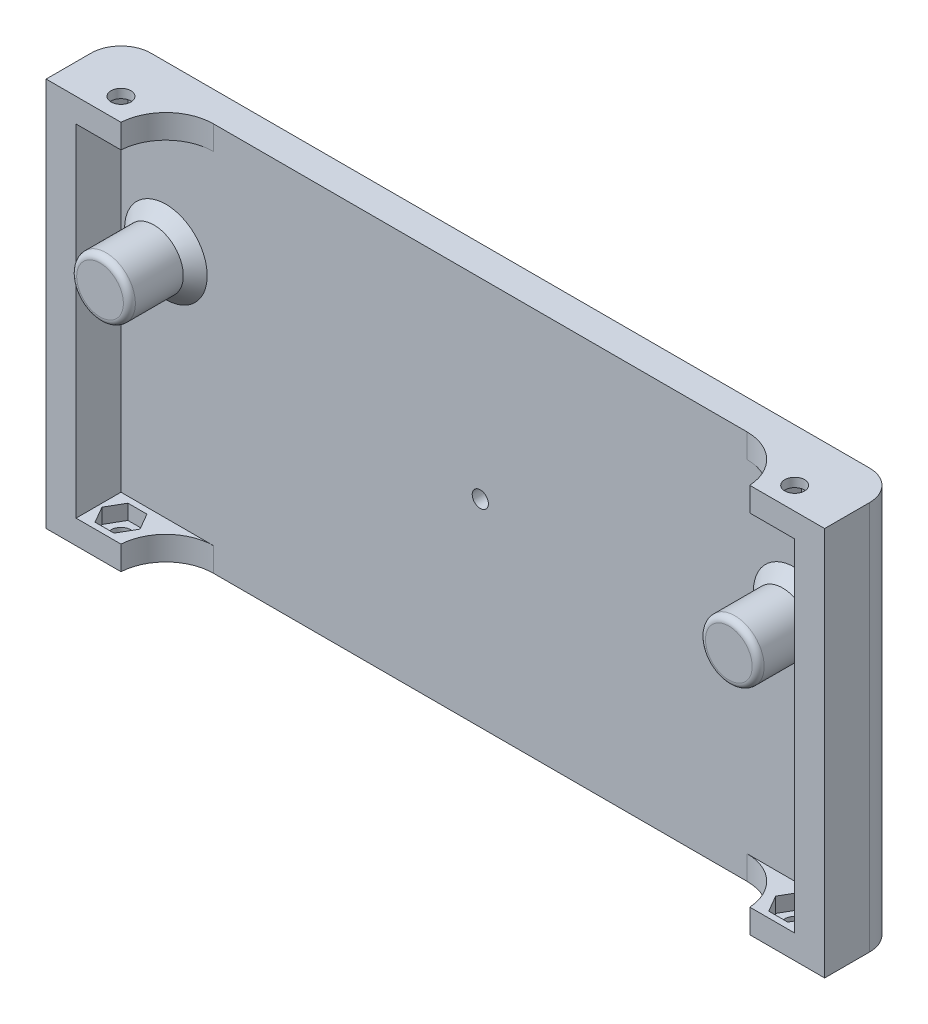
SolidWorks part; units mm, degrees
ref_plane "Front Plane" through (0, 0, 0) normal (0, 0, 1) x (1, 0, 0)
ref_plane "Top Plane" through (0, 0, 0) normal (0, 1, 0) x (1, 0, 0)
ref_plane "Right Plane" through (0, 0, 0) normal (1, 0, 0) x (0, 0, -1)
sketch "Sketch1" plane through (0, 0, 0) normal (0, 0, 1) x (1, 0, 0)
  line L1 (0, 0) -> (130, 0)
  line L2 (0, 0) -> (0, 65)
  line L3 (0, 65) -> (130, 65)
  line L4 (130, 0) -> (130, 65)
  dimension "D1" = 65
  dimension "D2" = 130
extrude "Boss-Extrude1" add sketch "Sketch1" along normal blind 12.5
sketch "Sketch3" plane through (0, 65, 0) normal (0, 1, 0) x (1, 0, 0)
  line L0 (5, -12.5) -> (125, -12.5)
  line L9 (125, -5) -> (125, -12.5)
  line L10 (5, -5) -> (125, -5)
  line L11 (5, -12.5) -> (5, -5)
  line L12 (125, -5) -> (125, -12.5)
  line L13 (5, -5) -> (125, -5)
  line L14 (5, -12.5) -> (5, -5)
  dimension "D1" = 5
extrude "Cut-Extrude1" cut sketch "Sketch3" against normal through all
fillet "Fillet1" radius 5 2 edges at (130, 32.5, 0) (0, 32.5, 0)
sketch "Sketch4" plane through (0, 0, 0) normal (0, -1, 0) x (1, 0, 0)
  line L0 (125, 5) -> (5, 5) construction
  line L1 (5, 12.5) -> (12.5, 12.5)
  line L2 (5, 12.5) -> (5, 5)
  line L3 (5, 5) -> (12.5, 5)
  line L4 (12.5, 12.5) -> (12.5, 5)
  line L6 (125, 5) -> (117.5, 5)
  line L7 (125, 5) -> (125, 12.5)
  line L8 (125, 12.5) -> (117.5, 12.5)
  line L9 (117.5, 5) -> (117.5, 12.5)
extrude "Boss-Extrude2" add sketch "Sketch4" against normal blind 4
sketch "Sketch5" plane through (0, 4, 0) normal (0, 1, 0) x (1, 0, 0)
  line L0 (121.25, -5) -> (121.25, -12.5) construction
  line L1 (117.5, -5) -> (125, -5) construction
  line L2 (125, -12.5) -> (117.5, -12.5) construction
  line L3 (65, 0) -> (65, -12.5) construction
  line L4 (124.4254, -8.75) -> (122.8377, -6)
  line L5 (122.8377, -6) -> (119.6623, -6)
  line L6 (119.6623, -6) -> (118.0746, -8.75)
  line L7 (118.0746, -8.75) -> (119.6623, -11.5)
  line L8 (119.6623, -11.5) -> (122.8377, -11.5)
  line L9 (122.8377, -11.5) -> (124.4254, -8.75)
  line L10 (125, 0) -> (5, 0) construction
  line L11 (10.3377, -6) -> (11.9254, -8.75)
  line L12 (11.9254, -8.75) -> (10.3377, -11.5)
  line L13 (7.1623, -11.5) -> (5.5746, -8.75)
  line L14 (10.3377, -11.5) -> (7.1623, -11.5)
  line L15 (7.1623, -6) -> (10.3377, -6)
  line L16 (5.5746, -8.75) -> (7.1623, -6)
  circle A0 centre (121.25, -8.75) radius 2.75 construction
  circle A1 centre (121.25, -8.75) radius 1.65
  circle A2 centre (8.75, -8.75) radius 1.65
  dimension "D2" = 3.3
  dimension "D1" = 5.5
extrude "Cut-Extrude2" cut sketch "Sketch5" against normal blind 2.5
extrude "Cut-Extrude3" cut sketch "Sketch5<3>" against normal through all contours A2 | A1 region at (121.25, 4, 8.75) region at (8.75, 4, 8.75)
sketch "Sketch5<3>" plane through (0, 4, 0) normal (0, 1, 0) x (1, 0, 0) same geometry as "Sketch5"
fillet "Fillet2" radius 8 2 edges at (117.5, 2, 5) (12.5, 2, 5)
ref_plane "Plane1" through (0, 32.5, 0) normal (0, 1, 0) x (1, 0, 0)
mirror "Mirror1" about plane through (0, 32.5, 0) normal (0, 1, 0) of "Cut-Extrude3", "Cut-Extrude2", "Boss-Extrude2", "Fillet2"
sketch "Sketch7" plane through (0, 0, 5) normal (0, 0, 1) x (1, 0, 0)
  line L0 (130, 0) -> (117.5, 0) construction
  line L1 (109.5156, 0) -> (20.4844, 0) construction
  line L2 (117.5, 0) -> (117.5, 42.5) construction
  line L3 (65, 65) -> (65, 0) construction
  line L4 (109.5156, 65) -> (20.4844, 65) construction
  circle A0 centre (117.5, 42.5) radius 4.9
  circle A1 centre (12.5, 42.5) radius 4.9
  dimension "D3" = 9.8
  dimension "D1" = 12.5
  dimension "D2" = 42.5
extrude "Boss-Extrude3" add sketch "Sketch7" along normal blind 11
fillet "Fillet3" radius 1 2 edges at (122.4, 42.5, 16) (7.6, 42.5, 16)
chamfer "Chamfer1" distance 2 angle 45 2 edges at (112.6, 42.5, 5) (7.6, 42.5, 5)
sketch "Sketch8" plane through (0, 0, 0) normal (0, 0, -1) x (-1, 0, 0)
  line L0 (-65, 65) -> (-65, 33) construction
  line L1 (-125, 65) -> (-5, 65) construction
  circle A0 centre (-65, 33) radius 1.35
  dimension "D2" = 2.7
  dimension "D1" = 32
extrude "Cut-Extrude4" cut sketch "Sketch8" against normal through all
